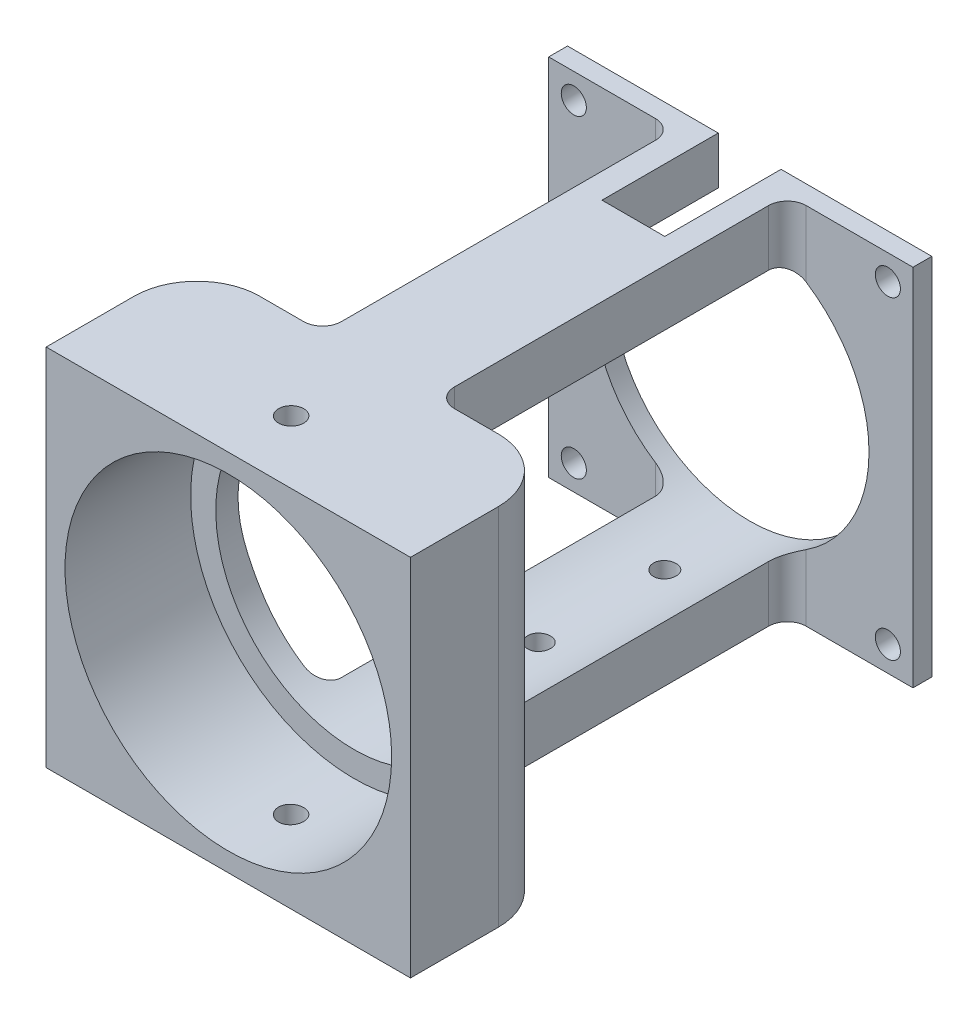
SolidWorks part; units mm, degrees
ref_plane "前视基准面" through (0, 0, 0) normal (0, 0, 1) x (1, 0, 0)
ref_plane "上视基准面" through (0, 0, 0) normal (0, 1, 0) x (1, 0, 0)
ref_plane "右视基准面" through (0, 0, 0) normal (1, 0, 0) x (0, 0, -1)
sketch "草图1" plane through (0, 0, 0) normal (0, 1, 0) x (1, 0, 0)
  line L0 (-29, 38.5) -> (-9, 38.5)
  line L1 (-29, -41.5) -> (29, -41.5)
  line L2 (-29, -41.5) -> (-29, -27.5)
  line L3 (-29, 41.5) -> (29, 41.5)
  line L4 (29, -41.5) -> (29, -27.5)
  line L5 (-29, -41.5) -> (29, 41.5) construction
  line L6 (-29, 41.5) -> (29, -41.5) construction
  line L7 (-19, -17.5) -> (-9, -17.5)
  line L9 (-9, -17.5) -> (-9, 38.5)
  line L11 (9, -17.5) -> (9, 38.5)
  line L12 (0, 0) -> (9, 38.5) construction
  line L13 (-9, 38.5) -> (0, 0) construction
  line L14 (-29, 38.5) -> (-29, 41.5)
  line L15 (29, 38.5) -> (29, 41.5)
  line L16 (9, 38.5) -> (29, 38.5)
  line L17 (9, -17.5) -> (19, -17.5)
  arc A0 (19, -17.5) -> (29, -27.5) centre (19, -27.5) cw
  arc A1 (-19, -17.5) -> (-29, -27.5) centre (-19, -27.5) ccw
  circle A2 centre (0, -31.5) radius 2
  point P0 (0, 0)
  point P8 (0, 0)
  dimension "D6" = 10
  dimension "D7" = 4
  dimension "D8" = 10
  dimension "D1" = 18
  dimension "D2" = 58
  dimension "D3" = 3
  dimension "D4" = 83
  dimension "D5" = 56
extrude "凸台-拉伸1" add sketch "草图1" along normal blind 58
sketch "草图2" plane through (0, 0, -41.5) normal (0, 0, -1) x (-1, 0, 0)
  line L0 (-29, 58) -> (29, 0) construction
  line L1 (-29, 0) -> (29, 58) construction
  circle A0 centre (0, 29) radius 22
  dimension "D1" = 44
extrude "切除-拉伸1" cut sketch "草图2" against normal blind 89
sketch "草图3" plane through (0, 0, 41.5) normal (0, 0, 1) x (1, 0, 0)
  circle A0 centre (0, 29) radius 26
  dimension "D1" = 52
extrude "切除-拉伸2" cut sketch "草图3" against normal blind 20
fillet "圆角1" radius 3 8 edges at (-9, 4.4626, 17.5) (-9, 53.5374, 17.5) (-9, 4.4626, -38.5) (-9, 53.5374, -38.5) (9, 4.4626, 17.5) (9, 53.5374, 17.5) (9, 4.4626, -38.5) (9, 53.5374, -38.5)
sketch "草图4" plane through (0, 0, -41.5) normal (0, 0, -1) x (-1, 0, 0)
  line L1 (-25, 4) -> (25, 4) construction
  line L2 (-25, 4) -> (-25, 54) construction
  line L3 (-25, 54) -> (25, 54) construction
  line L4 (25, 4) -> (25, 54) construction
  line L5 (-25, 4) -> (25, 54) construction
  line L6 (-25, 54) -> (25, 4) construction
  circle A0 centre (-25, 54) radius 2
  circle A1 centre (25, 54) radius 2
  circle A2 centre (25, 4) radius 2
  circle A3 centre (-25, 4) radius 2
  point P0 (0, 29)
  dimension "D3" = 4
  dimension "D1" = 50
  dimension "D2" = 50
extrude "切除-拉伸3" cut sketch "草图4" against normal blind 20
sketch "草图5" plane through (0, 0, 0) normal (0, -1, 0) x (1, 0, 0)
  line L0 (0, 41.5) -> (0, -41.5) construction
  line L1 (-29, 41.5) -> (29, 41.5) construction
  line L2 (29, -41.5) -> (-29, -41.5) construction
  circle A0 centre (0, 12) radius 1.8
  circle A1 centre (0, -8) radius 1.8
  circle A2 centre (0, -28) radius 1.8
  dimension "D1" = 3.6
  dimension "D2" = 29.5
  dimension "D3" = 20
  dimension "D4" = 20
extrude "切除-拉伸4" cut sketch "草图5" against normal blind 20
sketch "草图6" plane through (0, 0, 0) normal (1, 0, 0) x (0, 0, -1)
  circle A0 centre (64.5, 71) radius 43.5
  dimension "D1" = 87
extrude "切除-拉伸5" cut sketch "草图6" against normal blind 5 and the other way blind 5
